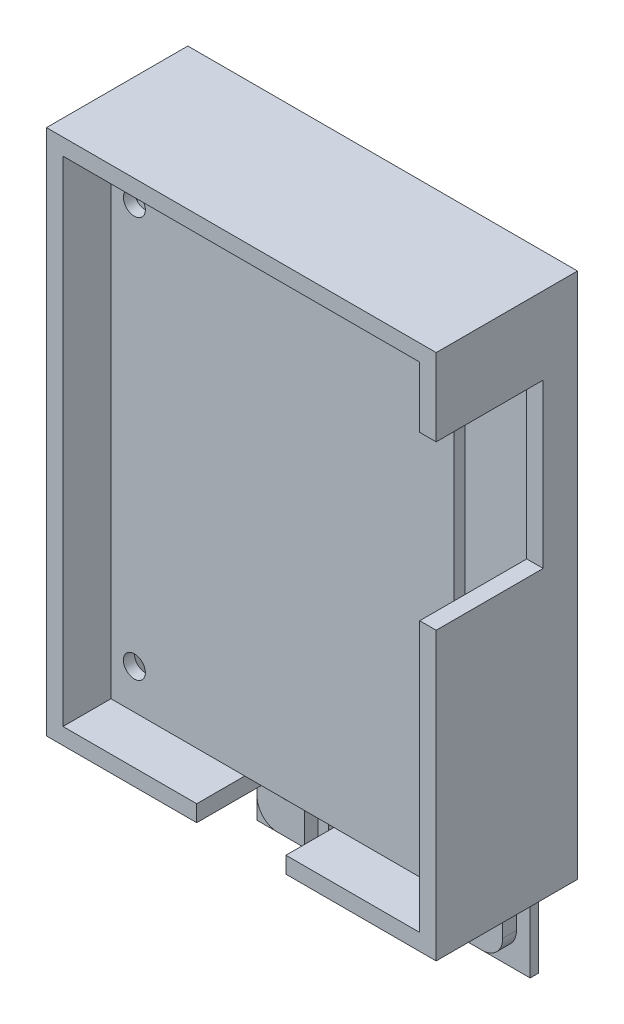
SolidWorks part; units mm, degrees
other "Switch-Cover"
other "ESP32"
other "Box"
other "PCB"
ref_plane "Front Plane" through (0, 0, 0) normal (0, 0, 1) x (1, 0, 0)
ref_plane "Top Plane" through (0, 0, 0) normal (0, 1, 0) x (1, 0, 0)
ref_plane "Right Plane" through (0, 0, 0) normal (1, 0, 0) x (0, 0, -1)
sketch "Sketch1" plane through (0, 0, 0) normal (0, 0, 1) x (1, 0, 0)
  line L1 (-25, -35) -> (25, -35)
  line L2 (-25, -35) -> (-25, 35)
  line L3 (-25, 35) -> (25, 35)
  line L4 (25, -35) -> (25, 35)
  line L5 (0, 35) -> (0, -35) construction
  line L6 (-25, 0) -> (25, 0) construction
  line L7 (-21.59, -29.21) -> (21.59, -29.21) construction
  line L8 (-21.59, -29.21) -> (-21.59, 29.21) construction
  line L9 (-21.59, 29.21) -> (21.59, 29.21) construction
  line L10 (21.59, -29.21) -> (21.59, 29.21) construction
  line L11 (0, 29.21) -> (0, -29.21) construction
  line L12 (-21.59, 0) -> (21.59, 0) construction
  circle A0 centre (-21.59, 29.21) radius 1.6
  circle A1 centre (21.59, 29.21) radius 1.6
  circle A2 centre (21.59, -29.21) radius 1.6
  circle A3 centre (-21.59, -29.21) radius 1.6
  point P0 (0, 0)
  point P4 (0, 0)
  dimension "D1" = 3.2
  dimension "D2" = 50
  dimension "D3" = 70
  dimension "D4" = 43.18
  dimension "D5" = 58.42
extrude "Boss-Extrude1" add sketch "Sketch1" along normal blind 1.6
ref_plane "Plane1" through (0, 0, -12.6) normal (0, 0, -1) x (-1, 0, 0)
ref_plane "Plane2" through (0, 0, 7.6) normal (0, 0, 1) x (1, 0, 0)
sketch "Sketch2" plane through (0, 0, 7.6) normal (0, 0, 1) x (1, 0, 0)
  line L4 (28.4, -38.4) -> (28.4, 38.4)
  line L5 (28.4, 38.4) -> (-28.4, 38.4)
  line L6 (-28.4, 38.4) -> (-28.4, -38.4)
  line L7 (-28.4, -38.4) -> (28.4, -38.4)
  line L8 (26, -36) -> (26, 36)
  line L9 (-26, -36) -> (26, -36)
  line L10 (-26, 36) -> (-26, -36)
  line L11 (26, 36) -> (-26, 36)
  line L12 (26, -36) -> (26, 36)
  line L13 (-26, -36) -> (26, -36)
  line L14 (-26, 36) -> (-26, -36)
  line L15 (26, 36) -> (-26, 36)
  point P4 (0, 0)
  dimension "D1" = 1
  dimension "D2" = 2.4
extrude "Boss-Extrude2" add sketch "Sketch2" against normal up to surface (20.2 mm away) separate body up to plane "Plane1"
sketch "Sketch3" plane through (0, 0, -12.6) normal (0, 0, -1) x (-1, 0, 0)
  line L1 (-28.4, -38.4) -> (28.4, -38.4)
  line L2 (-28.4, -38.4) -> (-28.4, 38.4)
  line L3 (-28.4, 38.4) -> (28.4, 38.4)
  line L4 (28.4, -38.4) -> (28.4, 38.4)
  line L5 (0, 38.4) -> (0, -38.4) construction
  line L6 (-28.4, 0) -> (28.4, 0) construction
  circle A0 centre (-21.59, -29.21) radius 1.6 construction
  circle A1 centre (21.59, -29.21) radius 1.6 construction
  circle A2 centre (21.59, 29.21) radius 1.6 construction
  circle A3 centre (-21.59, 29.21) radius 1.6 construction
  circle A4 centre (-21.59, -29.21) radius 1.6
  circle A5 centre (21.59, -29.21) radius 1.6
  circle A6 centre (21.59, 29.21) radius 1.6
  circle A7 centre (-21.59, 29.21) radius 1.6
  point P0 (0, 0)
  point P4 (0, 0)
extrude "Boss-Extrude3" add sketch "Sketch3" along normal blind 2
ref_plane "Plane3" through (0, 0, -7.7) normal (0, 0, -1) x (-1, 0, 0)
sketch "Sketch4" plane through (0, 0, -7.7) normal (0, 0, -1) x (-1, 0, 0)
  line L0 (21.59, 2.65) -> (21.59, 1.27) construction
  line L1 (-9.41, -15.35) -> (25.59, -15.35)
  line L2 (-9.41, -15.35) -> (-9.41, 2.65)
  line L3 (-9.41, 2.65) -> (25.59, 2.65)
  line L4 (25.59, -15.35) -> (25.59, 2.65)
  line L5 (8.09, 2.65) -> (8.09, -15.35) construction
  line L6 (-9.41, -6.35) -> (25.59, -6.35) construction
  line L7 (21.59, 1.27) -> (21.59, -13.97) construction
  line L8 (21.59, -13.97) -> (21.59, -15.35) construction
  line L9 (21.59, -29.21) -> (21.59, 29.21) construction
  line L10 (21.59, 29.21) -> (-21.59, 29.21) construction
  point P0 (8.09, -6.35)
  point P10 (0, 0)
  point P13 (34.7237, 2.65)
  point P14 (0, 0)
  dimension "D1" = 18
  dimension "D2" = 15.24
  dimension "D3" = 4
  dimension "D4" = 35
  dimension "D5" = 27.94
extrude "Boss-Extrude4" add sketch "Sketch4" along normal blind 1 separate body
sketch "Sketch5" plane through (-26, 0, 0) normal (1, 0, 0) x (0, 0, -1)
  line L0 (14.9, 1.15) -> (14.9, 4.65)
  line L1 (0.5, 10) -> (5.5, 10)
  line L2 (0.5, 10) -> (0.5, 25)
  line L3 (0.5, 25) -> (5.5, 25)
  line L4 (5.5, 10) -> (5.5, 25)
  line L5 (3, 25) -> (3, 10) construction
  line L6 (0.5, 17.5) -> (5.5, 17.5) construction
  line L7 (11.9, -10.85) -> (8.7, -10.85) construction
  line L8 (11.9, -10.85) -> (11.9, -1.85) construction
  line L9 (11.9, -1.85) -> (8.7, -1.85) construction
  line L10 (8.7, -10.85) -> (8.7, -1.85) construction
  line L11 (10.3, -1.85) -> (10.3, -10.85) construction
  line L12 (11.9, -6.35) -> (8.7, -6.35) construction
  line L13 (5.7, -13.85) -> (14.9, -13.85)
  line L14 (5.7, -13.85) -> (5.7, 1.15)
  line L15 (5.7, 1.15) -> (14.9, 1.15) construction
  line L16 (14.9, -13.85) -> (14.9, 1.15)
  line L17 (10.3, 1.15) -> (10.3, -13.85) construction
  line L18 (5.7, -6.35) -> (14.9, -6.35) construction
  line L19 (14.9, 4.65) -> (5.7, 4.65)
  line L20 (5.7, 4.65) -> (5.7, 1.15)
  line L21 (8.7, -15.35) -> (8.7, 2.65) construction
  line L22 (8.7, 2.65) -> (7.7, 2.65) construction
  line L23 (11.9, -10.85) -> (14.9, -10.85) construction
  line L24 (11.9, -10.85) -> (11.9, -13.85) construction
  line L26 (0, -35) -> (0, 35) construction
  point P0 (3, 17.5)
  point P4 (10.3, -6.35)
  point P8 (10.3, -6.35)
  point P19 (12.5, -13.85)
  dimension "D1" = 3.2
  dimension "D2" = 3
  dimension "D3" = 9
  dimension "D4" = 2
  dimension "D5" = 3
  dimension "D6" = 15
  dimension "D7" = 17.5
  dimension "D8" = 5
extrude "Cut-Extrude1" cut sketch "Sketch5" against normal through all and the other way blind 2
sketch "Sketch6" plane through (0, -36, 0) normal (0, 1, 0) x (1, 0, 0)
  line L0 (-26, -7.6) -> (26, -7.6) construction
  line L1 (-6.5, 8) -> (6.5, 8)
  line L2 (-6.5, 8) -> (-6.5, -7.6)
  line L3 (-6.5, -7.6) -> (6.5, -7.6)
  line L4 (6.5, 8) -> (6.5, -7.6)
  line L5 (0, -7.6) -> (0, 8) construction
  line L6 (-6.5, 0.2) -> (6.5, 0.2) construction
  line L8 (-25, 0) -> (25, 0) construction
  point P0 (0, 0.2)
  dimension "D1" = 8
  dimension "D2" = 13
extrude "Cut-Extrude2" cut sketch "Sketch6" against normal through all
sketch "Sketch7" plane through (26, 0, 0) normal (-1, 0, 0) x (0, 0, 1)
  line L0 (7.6, -36) -> (7.6, 36) construction
  line L1 (-8, 27.13) -> (7.6, 27.13)
  line L2 (-8, 27.13) -> (-8, 3.35)
  line L3 (-8, 3.35) -> (7.6, 3.35)
  line L4 (7.6, 27.13) -> (7.6, 3.35)
  line L5 (-0.2, 3.35) -> (-0.2, 27.13) construction
  line L6 (-8, 15.24) -> (7.6, 15.24) construction
  line L8 (4.5593, 27.13) -> (4.5593, 24.13) construction
  line L9 (4.5593, 24.13) -> (4.5593, 21.59) construction
  line L10 (4.5593, 21.59) -> (4.5593, 19.05) construction
  line L11 (4.5593, 19.05) -> (4.5593, 16.51) construction
  line L12 (4.5593, 16.51) -> (4.5593, 13.97) construction
  line L13 (4.5593, 13.97) -> (4.5593, 11.43) construction
  line L14 (4.5593, 11.43) -> (4.5593, 8.89) construction
  line L15 (4.5593, 8.89) -> (4.5593, 6.35) construction
  line L16 (4.5593, 6.35) -> (4.5593, 3.35) construction
  line L17 (0, -35) -> (0, 35) construction
  point P6 (4.7007, -9.6797)
  point P10 (0, 0)
  point P27 (0, 0)
  point P28 (0, 0)
  point P29 (0, 0)
  point P216 (-0.2, 15.24)
  dimension "D1" = 3
  dimension "D2" = 2.54
  dimension "D3" = 5.08
  dimension "D4" = 8
  dimension "D5" = 7
extrude "Cut-Extrude3" cut sketch "Sketch7" against normal through all
sketch "Sketch11" plane through (0, 0, -12.6) normal (0, 0, 1) x (1, 0, 0)
  line L0 (9.41, -15.35) -> (9.41, 2.65) construction
  line L2 (9.41, 2.65) -> (-25.59, 2.65) construction
  line L3 (-24, 4.65) -> (-22.59, 4.65)
  line L4 (-22.59, 4.65) -> (-22.59, -0.95)
  line L5 (-22.59, -0.95) -> (-24, -2.36)
  line L6 (-24, -13.85) -> (-24, 4.65) construction
  line L7 (-24, -2.36) -> (-24, 4.65)
  line L10 (-25.59, -15.35) -> (-25.59, 2.65) construction
  circle A0 centre (7.41, -4.35) radius 4
  point P9 (-22.59, 1.85)
  dimension "D1" = 8
  dimension "D2" = 2
  dimension "D3" = 7
  dimension "D4" = 45
  dimension "D5" = 0.8
  dimension "D6" = 3
extrude "Cut-Extrude5" cut sketch "Sketch11" against normal through all
sketch "Sketch8" plane through (0, 0, -14.6) normal (0, 0, -1) x (-1, 0, 0)
  line L0 (0, 35) -> (0, -35) construction
  line L1 (-19.9, -39.4) -> (19.9, -39.4)
  line L2 (-19.9, -39.4) -> (-19.9, -55.9)
  line L3 (-19.9, -55.9) -> (19.9, -55.9)
  line L4 (19.9, -39.4) -> (19.9, -55.9)
  line L5 (0, -55.9) -> (0, -39.4) construction
  line L6 (-19.9, -47.65) -> (19.9, -47.65) construction
  line L7 (28.4, -38.4) -> (-28.4, -38.4) construction
  line L9 (-9.5, -54.15) -> (9.5, -54.15)
  line L10 (-9.5, -54.15) -> (-9.5, -41.15)
  line L11 (-9.5, -41.15) -> (9.5, -41.15)
  line L12 (9.5, -54.15) -> (9.5, -41.15)
  line L13 (0, -41.15) -> (0, -54.15) construction
  line L14 (-9.5, -47.65) -> (9.5, -47.65) construction
  point P0 (0, -47.65)
  point P11 (0, -47.65)
  dimension "D1" = 16.5
  dimension "D2" = 39.8
  dimension "D3" = 1
  dimension "D4" = 13
  dimension "D5" = 19
extrude "Boss-Extrude5" add sketch "Sketch8" along normal blind 1.2 separate body
sketch "Sketch9" plane through (0, 0, -14.6) normal (0, 0, -1) x (-1, 0, 0)
  line L0 (-19.9, -47.65) -> (19.9, -47.65) construction
  line L1 (-17.9, -53.9) -> (-11, -53.9)
  line L2 (-17.9, -53.9) -> (-17.9, -41.4)
  line L3 (-17.9, -41.4) -> (-11, -41.4)
  line L4 (-11, -53.9) -> (-11, -41.4)
  line L5 (-14.45, -41.4) -> (-14.45, -53.9) construction
  line L6 (-17.9, -47.65) -> (-11, -47.65) construction
  line L7 (11, -53.9) -> (17.9, -53.9)
  line L8 (11, -53.9) -> (11, -41.4)
  line L9 (11, -41.4) -> (17.9, -41.4)
  line L10 (17.9, -53.9) -> (17.9, -41.4)
  line L11 (14.45, -41.4) -> (14.45, -53.9) construction
  line L12 (11, -47.65) -> (17.9, -47.65) construction
  line L13 (-11, -41.4) -> (11, -41.4) construction
  line L14 (0, -55.9) -> (0, -39.4) construction
  line L15 (-19.9, -39.4) -> (19.9, -39.4) construction
  line L16 (-19.9, -39.4) -> (-19.9, -55.9) construction
  point P0 (-14.45, -47.65)
  point P4 (14.45, -47.65)
  point P10 (0, -41.4)
  dimension "D1" = 22
  dimension "D2" = 2
  dimension "D3" = 2
extrude "Boss-Extrude6" add sketch "Sketch9" against normal blind 2
sketch "Sketch10" plane through (0, 0, -12.6) normal (0, 0, 1) x (1, 0, 0)
  line L0 (-16.95, -49.15) -> (-12.7572, -49.15) construction
  line L1 (19.9, -47.65) -> (-19.9, -47.65) construction
  line L2 (-14.45, -41.4) -> (-14.45, -53.9) construction
  line L3 (12.75, -49.15) -> (16.8724, -49.15) construction
  line L4 (14.45, -41.4) -> (14.45, -53.9) construction
  text T0 "<b>IG</b>"
  text T1 "<b>A</b>"
  dimension "D1" = 1.5
  dimension "D2" = 2.5
  dimension "D3" = 1.7
extrude "Cut-Extrude4" cut sketch "Sketch10" against normal blind 2
fillet "Fillet1" radius 3 4 edges at (17.9, -41.4, -13.6) (17.9, -53.9, -13.6) (-17.9, -53.9, -13.6) (-17.9, -41.4, -13.6)
chamfer "Chamfer1" distance 1.6 angle 45 5 edges at (-28.4, -26.125, -14.6) (0, -38.4, -14.6) (28.4, 0, -14.6) (0, 38.4, -14.6) (-28.4, 21.525, -14.6)
